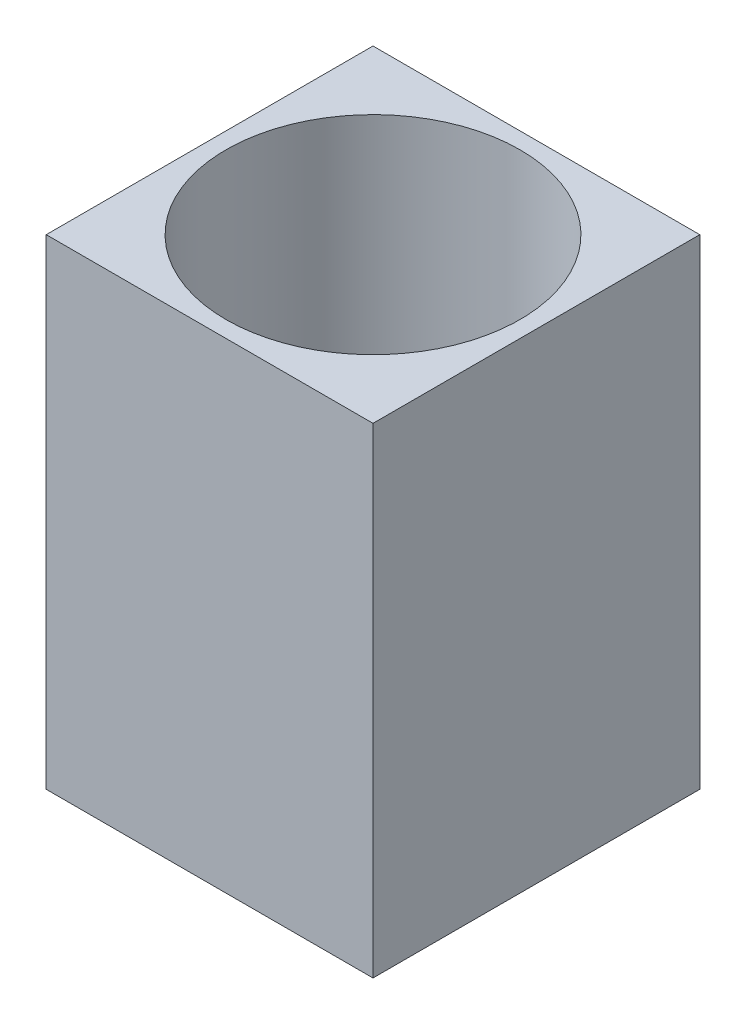
SolidWorks part; units mm, degrees
ref_plane "Front Plane" through (0, 0, 0) normal (0, 0, 1) x (1, 0, 0)
ref_plane "Top Plane" through (0, 0, 0) normal (0, 1, 0) x (1, 0, 0)
ref_plane "Right Plane" through (0, 0, 0) normal (1, 0, 0) x (0, 0, -1)
sketch "Sketch1" plane through (0, 0, 0) normal (0, 1, 0) x (1, 0, 0)
  line L1 (0, 0) -> (10, 0)
  line L2 (0, 0) -> (0, -10)
  line L3 (0, -10) -> (10, -10)
  line L4 (10, 0) -> (10, -10)
  circle A0 centre (5, -5) radius 4.5
  point P8 (5, 0)
  point P10 (0, -5)
  dimension "D3" = 9
  dimension "D1" = 10
  dimension "D2" = 10
extrude "Boss-Extrude1" add sketch "Sketch1" along normal blind 14.7
